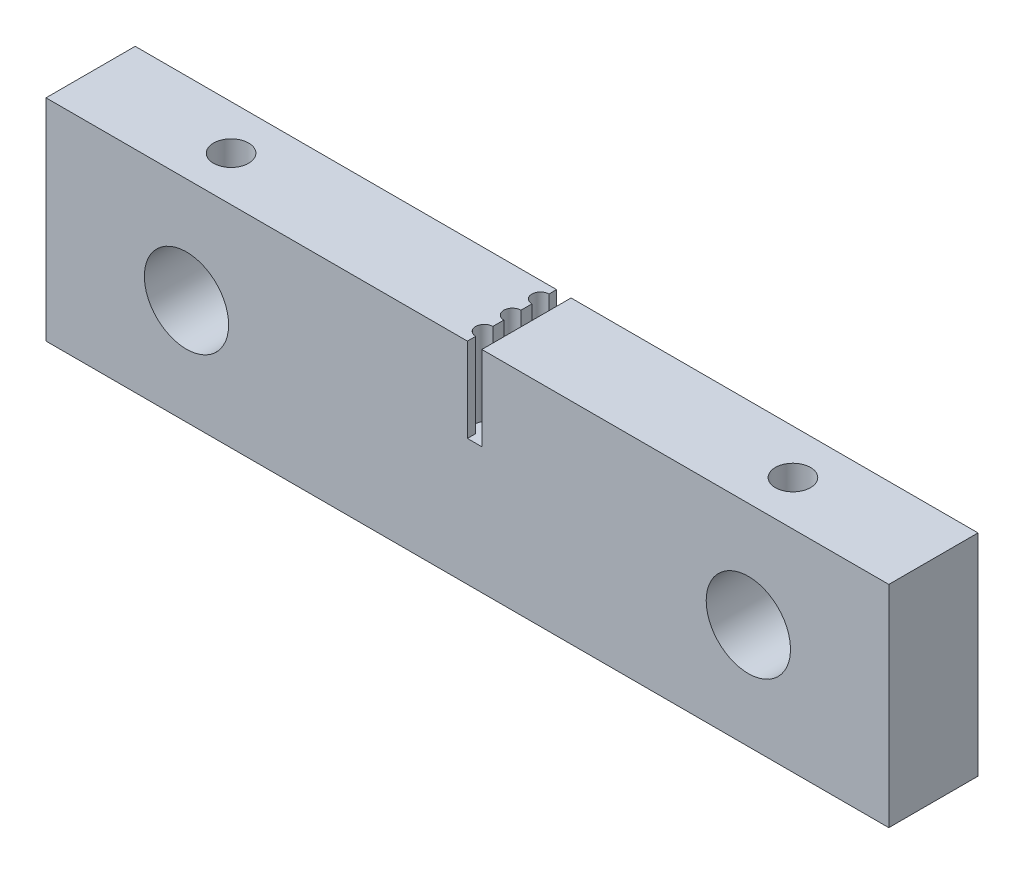
SolidWorks part; units mm, degrees
material "6061 Alloy"
ref_plane "Front Plane" through (0, 0, 0) normal (0, 0, 1) x (1, 0, 0)
ref_plane "Top Plane" through (0, 0, 0) normal (0, 1, 0) x (1, 0, 0)
ref_plane "Right Plane" through (0, 0, 0) normal (1, 0, 0) x (0, 0, -1)
sketch "Sketch1" plane through (0, 0, 0) normal (0, 0, 1) x (1, 0, 0)
  line L0 (30, 15) -> (30, 0) construction
  line L1 (0, 0) -> (60, 0)
  line L2 (0, 0) -> (0, 15)
  line L3 (0, 15) -> (60, 15)
  line L4 (60, 0) -> (60, 15)
  line L5 (0, 7.5) -> (60, 7.5) construction
  circle A0 centre (10, 7.5) radius 3
  circle A1 centre (50, 7.5) radius 3
  dimension "D3" = 6
  dimension "D1" = 60
  dimension "D2" = 15
  dimension "D4" = 40
extrude "Boss-Extrude1" add sketch "Sketch1" along normal blind 6.35
ref_axis "Axis1" through (10, 7.5, 6.35) along (0, 0, -1)
hole_wizard "M3 Tapped Hole1" positions "Sketch4" profile "Sketch3" tap size "M3" standard "ISO"
sketch "Sketch4" plane through (0, 15, 0) normal (0, 1, 0) x (-1, 0, 0)
  line L0 (0, 3.175) -> (-60, 3.175) construction
  line L1 (0, 6.35) -> (0, 0) construction
  line L2 (-60, 6.35) -> (-60, 0) construction
  line L5 (-30, 0) -> (-30, 6.35) construction
  line L6 (-60, 0) -> (0, 0) construction
  line L7 (-60, 6.35) -> (0, 6.35) construction
  line L10 (-10, 6.35) -> (-10, 0) construction
  point P0 (-10, 3.175)
  point P25 (-50, 3.175)
sketch "Sketch3" plane through (10, 15, 3.175) normal (1, 0, 0) x (0, 0, 1)
  line L0 (0, 0) -> (0, 9.2511)
  line L1 (0, 9.2511) -> (1.25, 8.5)
  line L2 (1.25, 8.5) -> (1.25, 0)
  line L5 (1.25, 0) -> (0, 0)
  line L10 (0, 9.2511) -> (-1.25, 8.5) construction
  line L11 (0, -6.35) -> (0, 107.95) construction
  dimension "Tap Drill Dia." = 2.5
  dimension "Tap Drill Depth" = 8.5
  dimension "Drill Angle" = 118
cosmetic thread "Hole Thread1" parameters "D1"=4.8642, "D2"=3
cosmetic thread "Hole Thread2" parameters "D1"=4.8642, "D2"=3
ref_plane "Plane1" through (30, 0, 0) normal (-1, 0, 0) x (0, 0, 1)
sketch "Sketch5" plane through (0, 15, 0) normal (0, 1, 0) x (1, 0, 0)
  line L0 (31.03, -6.35) -> (31.03, 0) construction
  line L1 (60, -6.35) -> (0, -6.35) construction
  line L2 (60, 0) -> (0, 0) construction
  line L3 (31.03, -6.35) -> (31.03, 0)
  line L4 (31.03, 0) -> (30, 0)
  line L5 (30, 0) -> (30, -0.5375)
  line L6 (30, -1.7575) -> (30, -2.5375)
  line L7 (30, -3.7575) -> (30, -4.5375)
  line L8 (30, -5.7575) -> (30, -6.35)
  line L9 (30, -6.35) -> (31.03, -6.35)
  arc A3 (30, -0.5375) -> (30, -1.7575) centre (30, -1.1475) ccw
  arc A4 (30, -2.5375) -> (30, -3.7575) centre (30, -3.1475) ccw
  arc A5 (30, -4.5375) -> (30, -5.7575) centre (30, -5.1475) ccw
  point P0 (30, 0)
  dimension "D1" = 2
  dimension "D4" = 0.61
  dimension "D2" = 2
  dimension "D3" = 1.03
extrude "Cut-Extrude1" cut sketch "Sketch5" against normal blind 6
